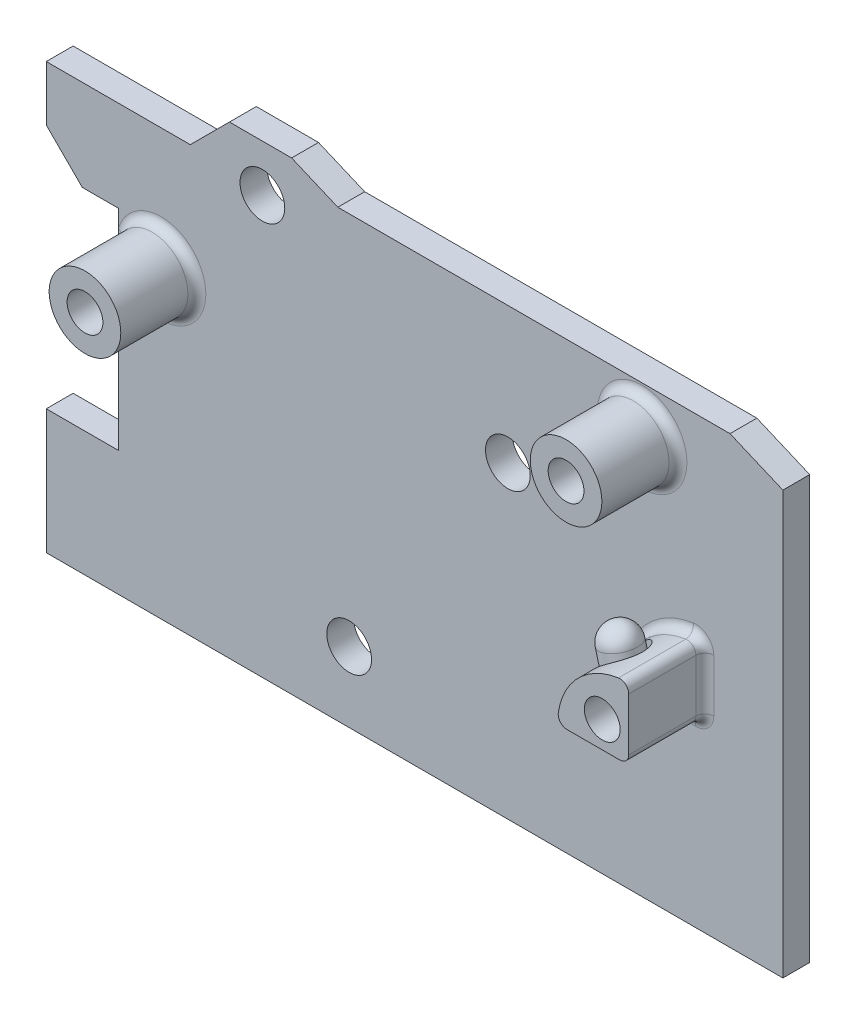
SolidWorks part; units mm, degrees
ref_plane "정면" through (0, 0, 0) normal (0, 0, 1) x (1, 0, 0)
ref_plane "윗면" through (0, 0, 0) normal (0, 1, 0) x (1, 0, 0)
ref_plane "우측면" through (0, 0, 0) normal (1, 0, 0) x (0, 0, -1)
sketch "스케치2" plane through (0, 0, 0) normal (0, 0, 1) x (1, 0, 0)
  line L0 (-41.1383, 21.5701) -> (-25.0531, 21.5701)
  line L1 (-25.0531, 21.5701) -> (-20.6777, 25.9456)
  line L2 (-20.6777, 25.9456) -> (-13.7287, 25.9456)
  line L3 (-13.7287, 25.9456) -> (-8.5741, 23.7579)
  line L4 (-8.5741, 23.7579) -> (35.2319, 23.7579)
  line L5 (35.2319, 23.7579) -> (41.1383, 21.2511)
  line L6 (41.1383, 21.2511) -> (41.1383, -25.9456)
  line L7 (41.1383, -25.9456) -> (-41.1383, -25.9456)
  line L8 (-41.1383, -25.9456) -> (-41.1383, -12.0209)
  line L9 (-41.1383, -12.0209) -> (-33.0957, -12.0209)
  line L10 (-33.0957, -12.0209) -> (-33.0957, 11.4038)
  line L11 (-33.0957, 11.4038) -> (-37.117, 11.4038)
  line L12 (-37.117, 11.4038) -> (-41.1383, 15.4251)
  line L13 (-41.1383, 15.4251) -> (-41.1383, 21.5701)
  line L14 (25.5434, -5.467) -> (31.4219, -5.467)
  line L15 (32.4219, -4.467) -> (32.4219, 1.4115)
  line L16 (32.1291, -5.1741) -> (26.7998, 0.1551) construction
  line L17 (0, 0) -> (-17, 0) construction
  line L18 (-17, 0) -> (-17, 20.7) construction
  circle A0 centre (-17, 20.7) radius 2.5
  circle A1 centre (-28.3144, 7.9767) radius 4
  circle A2 centre (25.4219, 18.533) radius 4
  circle A3 centre (-7.3061, -18.1076) radius 2.5
  circle A4 centre (10.4219, 8.533) radius 2.5
  circle A5 centre (-28.3144, 7.9767) radius 2
  circle A6 centre (25.4219, 18.533) radius 2
  arc A7 (31.2781, 2.4011) -> (24.5538, -4.3232) centre (32.4219, -5.467) ccw
  arc A8 (31.4219, -5.467) -> (32.4219, -4.467) centre (31.4219, -4.467) ccw
  arc A9 (32.4219, 1.4115) -> (31.2781, 2.4011) centre (31.4219, 1.4115) ccw
  arc A10 (25.5434, -5.467) -> (24.5538, -4.3232) centre (25.5434, -4.467) cw
  circle A11 centre (29.4644, -2.5095) radius 2
  point P36 (32.4219, 2.4838)
  point P39 (24.4711, -5.467)
  dimension "D1" = 1
  dimension "D5" = 5
  dimension "D6" = 5
  dimension "D7" = 5
  dimension "D12" = 4
  dimension "D13" = 4
  dimension "D14" = 8
  dimension "D15" = 8
  dimension "D18" = 4
  dimension "D2" = 30
  dimension "D3" = 40
  dimension "D4" = 32
  dimension "D8" = 20.7
  dimension "D9" = 17
  dimension "D10" = 10
  dimension "D11" = 15
  dimension "D16" = 22
  dimension "D17" = 14
  dimension "D19" = 8.0531
sketch "스케치3" plane through (0, 0, 0) normal (0, 0, 1) x (1, 0, 0)
extrude "보스-돌출1" add sketch "스케치2" along normal blind 3 contours L13 L12 L11 L10 L9 L8 L7 L6 L5 L4 L3 L2 L1 L0 A4 A3 A2 A1 A0 L14 A10 A7 A9 L15 A8 region at (1.8741, -1.7514, 0)
extrude "보스-돌출2" add sketch "스케치2<3>" along normal blind 11.5 contours A10 L14 A8 L15 A9 A7 A11 | A1 A5 | A2 | A6 region at (24.8714, -5.0484, 0) region at (-32.2013, 7.9767, 0)
sketch "스케치2<3>" plane through (0, 0, 0) normal (0, 0, 1) x (1, 0, 0) same geometry as "스케치2"
sketch "스케치5" plane through (0, 0, 11.5) normal (0, 0, 1) x (1, 0, 0)
  line L0 (32.1291, -5.1741) -> (28.79, 7.2872)
  line L2 (25.5434, -5.467) -> (31.4219, -5.467) construction
  arc A0 (31.4219, -5.467) -> (32.4219, -4.467) centre (31.4219, -4.467) ccw construction
  dimension "D1" = 75
ref_plane "평면1" through (1.4808, -5.5264, 0) normal (-0.2588, 0.9659, 0) x (0, 0, 1)
sketch "스케치6" plane through (1.4808, -5.5264, 0) normal (-0.2588, 0.9659, 0) x (0, 0, 1)
  line L0 (3, 30.8338) -> (11.5, 22.5982) construction
  circle A0 centre (7.25, 26.716) radius 2
extrude "보스-돌출3" add sketch "스케치6" along normal mid plane 4.6 contours A0
fillet "필렛1" radius 2 1 edges at (24.7593, 3.0922, 7.25)
sketch "스케치7" plane through (1.4808, -5.5264, 0) normal (-0.2588, 0.9659, 0) x (0, 0, 1)
  circle A0 centre (7.25, 26.716) radius 2.5
  circle A2 centre (7.25, 26.716) radius 2
extrude "컷-돌출2" cut sketch "스케치7" against normal blind 2
fillet "필렛2" radius 1 8 edges at (32.0762, 2.1678, 3) (32.4219, -1.5278, 3) (32.1291, -5.1741, 3) (28.4827, -5.467, 3) (24.7871, -5.1213, 3) (-24.3144, 7.9767, 3) (29.4219, 18.533, 3) (26.7998, 0.1551, 3)
